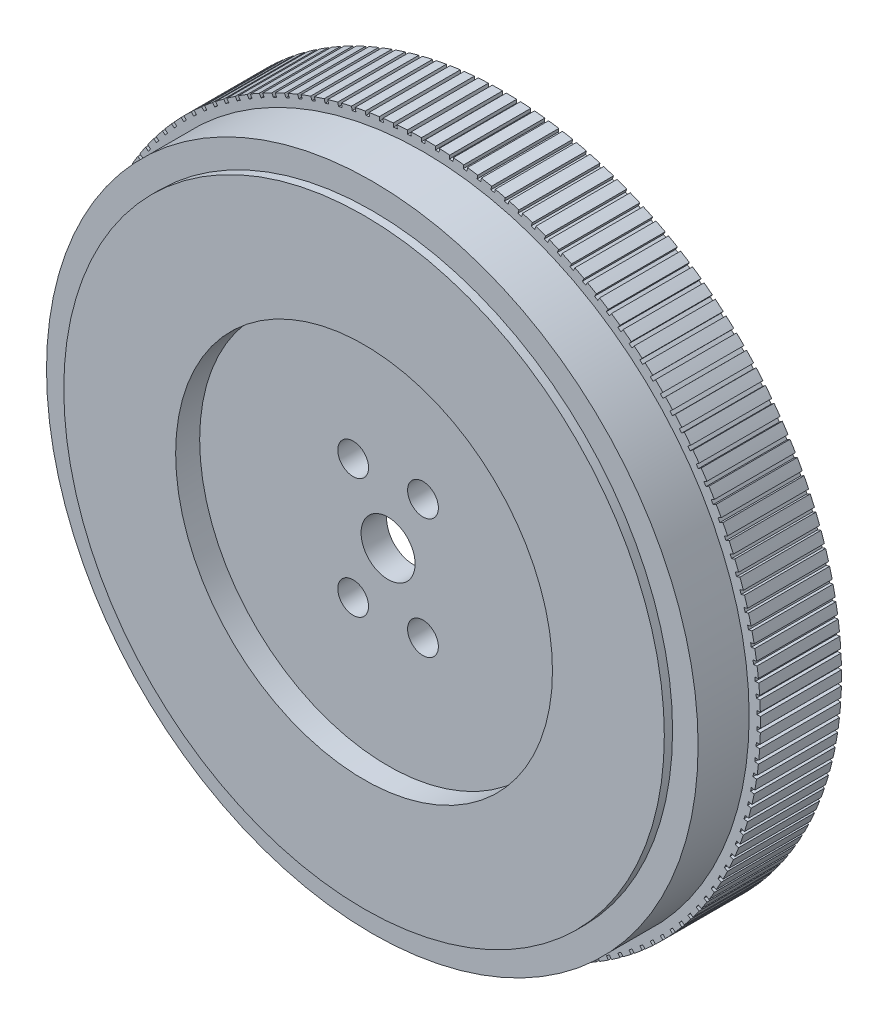
SolidWorks part; units mm, degrees
ref_plane "Front Plane" through (0, 0, 0) normal (0, 0, 1) x (1, 0, 0)
ref_plane "Top Plane" through (0, 0, 0) normal (0, 1, 0) x (1, 0, 0)
ref_plane "Right Plane" through (0, 0, 0) normal (1, 0, 0) x (0, 0, -1)
sketch "Sketch1" plane through (0, 0, 0) normal (0, 0, 1) x (1, 0, 0)
  circle A0 centre (0, 0) radius 25.1
  circle A1 centre (0, 0) radius 40
  circle A2 centre (0, 0) radius 43.4
  circle A3 centre (0, 0) radius 44.9
  dimension "D1" = 50.2
  dimension "D2" = 80
  dimension "D3" = 86.8
  dimension "D4" = 89.8
extrude "Boss-Extrude1" add sketch "Sketch1" along normal blind 10.8 contours A3
sketch "Sketch2" plane through (0, 0, 10.8) normal (0, 0, 1) x (1, 0, 0)
  circle A1 centre (0, 0) radius 44.9
  circle A3 centre (0, 0) radius 44.9
  circle A4 centre (0, 0) radius 43.4
  circle A5 centre (0, 0) radius 43.4
  dimension "D1" = 0
  dimension "D2" = 0
extrude "Boss-Extrude2" add sketch "Sketch2" along normal blind 6.8 contours A5 region at (0, 0, 10.8)
sketch "Sketch3" plane through (0, 0, 17.6) normal (0, 0, 1) x (1, 0, 0)
  circle A5 centre (0, 0) radius 40
  circle A6 centre (0, 0) radius 40
  dimension "D3" = 0
extrude "Boss-Extrude3" add sketch "Sketch3" along normal blind 1.1
sketch "Sketch4" plane through (0, 0, 18.7) normal (0, 0, 1) x (1, 0, 0)
  circle A8 centre (0, 0) radius 25.1
  circle A9 centre (0, 0) radius 25.1
  dimension "D4" = 0
extrude "Cut-Extrude1" cut sketch "Sketch4" against normal blind 3.2
sketch "Sketch5" plane through (0, 0, 0) normal (0, 0, -1) x (-1, 0, 0)
  circle A0 centre (0, 0) radius 33.85
  dimension "D1" = 67.7
extrude "Cut-Extrude2" cut sketch "Sketch5" against normal blind 12.1
sketch "Sketch6" plane through (0, 0, 15.5) normal (0, 0, 1) x (1, 0, 0)
  line L0 (0, 0) -> (0, 10.7681) construction
  line L1 (0, 0) -> (5.1297, 0) construction
  circle A0 centre (0, 0) radius 3.6
  circle A1 centre (4.65, 8) radius 2.05
  circle A2 centre (-4.65, 8) radius 2.05
  circle A3 centre (-4.65, -8) radius 2.05
  circle A4 centre (4.65, -8) radius 2.05
  dimension "D1" = 7.2
  dimension "D2" = 4.1
  dimension "D4" = 8
  dimension "D3" = 4.65
extrude "Cut-Extrude3" cut sketch "Sketch6" against normal through all
sketch "Sketch7" plane through (0, 0, 0) normal (0, 0, -1) x (-1, 0, 0)
  line L0 (0, -0.0504) -> (0, 18.0936) construction
  line L1 (1.6316, 44.8985) -> (1.6106, 44.3989)
  line L2 (-0.25, 44.9274) -> (0.25, 44.9274)
  line L3 (-0.25, 44.9274) -> (-0.25, 44.4274)
  line L4 (-0.25, 44.4274) -> (0.25, 44.4274)
  line L5 (0.25, 44.9274) -> (0.25, 44.4274)
  line L6 (-0.25, 44.9274) -> (0.25, 44.4274) construction
  line L7 (-0.25, 44.4274) -> (0.25, 44.9274) construction
  line L8 (1.6316, 44.8985) -> (2.1311, 44.8775)
  line L9 (2.1311, 44.8775) -> (2.1102, 44.378)
  line L10 (1.6106, 44.3989) -> (2.1102, 44.378)
  line L11 (3.5103, 44.7908) -> (3.4685, 44.2925)
  line L12 (3.5103, 44.7908) -> (4.0086, 44.7489)
  line L13 (4.0086, 44.7489) -> (3.9667, 44.2507)
  line L14 (3.4685, 44.2925) -> (3.9667, 44.2507)
  line L15 (5.3829, 44.6045) -> (5.3202, 44.1084)
  line L16 (5.3829, 44.6045) -> (5.8789, 44.5418)
  line L17 (5.8789, 44.5418) -> (5.8163, 44.0458)
  line L18 (5.3202, 44.1084) -> (5.8163, 44.0458)
  line L19 (7.246, 44.3399) -> (7.1626, 43.847)
  line L20 (7.246, 44.3399) -> (7.739, 44.2566)
  line L21 (7.739, 44.2566) -> (7.6556, 43.7636)
  line L22 (7.1626, 43.847) -> (7.6556, 43.7636)
  line L23 (9.0964, 43.9976) -> (8.9924, 43.5086)
  line L24 (9.0964, 43.9976) -> (9.5855, 43.8937)
  line L25 (9.5855, 43.8937) -> (9.4815, 43.4046)
  line L26 (8.9924, 43.5086) -> (9.4815, 43.4046)
  line L27 (10.9308, 43.5781) -> (10.8065, 43.0938)
  line L28 (10.9308, 43.5781) -> (11.4151, 43.4538)
  line L29 (11.4151, 43.4538) -> (11.2908, 42.9695)
  line L30 (10.8065, 43.0938) -> (11.2908, 42.9695)
  line L31 (12.7461, 43.0822) -> (12.6016, 42.6035)
  line L32 (12.7461, 43.0822) -> (13.2248, 42.9376)
  line L33 (13.2248, 42.9376) -> (13.0803, 42.459)
  line L34 (12.6016, 42.6035) -> (13.0803, 42.459)
  line L35 (14.539, 42.5106) -> (14.3746, 42.0384)
  line L36 (14.539, 42.5106) -> (15.0112, 42.3462)
  line L37 (15.0112, 42.3462) -> (14.8468, 41.874)
  line L38 (14.3746, 42.0384) -> (14.8468, 41.874)
  line L39 (16.3064, 41.8645) -> (16.1224, 41.3996)
  line L40 (16.3064, 41.8645) -> (16.7713, 41.6804)
  line L41 (16.7713, 41.6804) -> (16.5873, 41.2155)
  line L42 (16.1224, 41.3996) -> (16.5873, 41.2155)
  line L43 (18.0452, 41.1449) -> (17.8419, 40.6882)
  line L44 (18.0452, 41.1449) -> (18.502, 40.9416)
  line L45 (18.502, 40.9416) -> (18.2986, 40.4848)
  line L46 (17.8419, 40.6882) -> (18.2986, 40.4848)
  line L47 (19.7524, 40.3532) -> (19.5301, 39.9053)
  line L48 (19.7524, 40.3532) -> (20.2002, 40.1309)
  line L49 (20.2002, 40.1309) -> (19.9779, 39.683)
  line L50 (19.5301, 39.9053) -> (19.9779, 39.683)
  line L51 (21.4249, 39.4906) -> (21.184, 39.0525)
  line L52 (21.4249, 39.4906) -> (21.863, 39.2498)
  line L53 (21.863, 39.2498) -> (21.6221, 38.8116)
  line L54 (21.184, 39.0525) -> (21.6221, 38.8116)
  line L55 (23.0598, 38.5588) -> (22.8008, 38.1311)
  line L56 (23.0598, 38.5588) -> (23.4875, 38.2998)
  line L57 (23.4875, 38.2998) -> (23.2284, 37.8721)
  line L58 (22.8008, 38.1311) -> (23.2284, 37.8721)
  line L59 (24.6542, 37.5593) -> (24.3775, 37.1429)
  line L60 (24.6542, 37.5593) -> (25.0707, 37.2827)
  line L61 (25.0707, 37.2827) -> (24.794, 36.8662)
  line L62 (24.3775, 37.1429) -> (24.794, 36.8662)
  line L63 (26.2054, 36.494) -> (25.9115, 36.0895)
  line L64 (26.2054, 36.494) -> (26.6099, 36.2001)
  line L65 (26.6099, 36.2001) -> (26.316, 35.7956)
  line L66 (25.9115, 36.0895) -> (26.316, 35.7956)
  line L67 (27.7106, 35.3646) -> (27.4001, 34.9728)
  line L68 (27.7106, 35.3646) -> (28.1025, 35.054)
  line L69 (28.1025, 35.054) -> (27.7919, 34.6622)
  line L70 (27.4001, 34.9728) -> (27.7919, 34.6622)
  line L71 (29.1673, 34.1732) -> (28.8405, 33.7947)
  line L72 (29.1673, 34.1732) -> (29.5457, 33.8465)
  line L73 (29.5457, 33.8465) -> (29.219, 33.468)
  line L74 (28.8405, 33.7947) -> (29.219, 33.468)
  line L75 (30.5727, 32.9218) -> (30.2304, 32.5573)
  line L76 (30.5727, 32.9218) -> (30.9372, 32.5795)
  line L77 (30.9372, 32.5795) -> (30.5949, 32.2151)
  line L78 (30.2304, 32.5573) -> (30.5949, 32.2151)
  line L79 (31.9245, 31.6127) -> (31.5673, 31.2629)
  line L80 (31.9245, 31.6127) -> (32.2743, 31.2554)
  line L81 (32.2743, 31.2554) -> (31.9171, 30.9056)
  line L82 (31.5673, 31.2629) -> (31.9171, 30.9056)
  line L83 (33.2203, 30.2481) -> (32.8487, 29.9135)
  line L84 (33.2203, 30.2481) -> (33.5549, 29.8765)
  line L85 (33.5549, 29.8765) -> (33.1833, 29.542)
  line L86 (32.8487, 29.9135) -> (33.1833, 29.542)
  line L87 (34.4578, 28.8304) -> (34.0726, 28.5117)
  line L88 (34.4578, 28.8304) -> (34.7765, 28.4452)
  line L89 (34.7765, 28.4452) -> (34.3913, 28.1265)
  line L90 (34.0726, 28.5117) -> (34.3913, 28.1265)
  line L91 (35.6349, 27.3622) -> (35.2366, 27.0599)
  line L92 (35.6349, 27.3622) -> (35.9372, 26.9639)
  line L93 (35.9372, 26.9639) -> (35.5389, 26.6616)
  line L94 (35.2366, 27.0599) -> (35.5389, 26.6616)
  line L95 (36.7494, 25.846) -> (36.3389, 25.5606)
  line L96 (36.7494, 25.846) -> (37.0348, 25.4354)
  line L97 (37.0348, 25.4354) -> (36.6242, 25.15)
  line L98 (36.3389, 25.5606) -> (36.6242, 25.15)
  line L99 (37.7995, 24.2844) -> (37.3774, 24.0165)
  line L100 (37.7995, 24.2844) -> (38.0674, 23.8622)
  line L101 (38.0674, 23.8622) -> (37.6453, 23.5943)
  line L102 (37.3774, 24.0165) -> (37.6453, 23.5943)
  line L103 (38.7833, 22.6802) -> (38.3503, 22.4302)
  line L104 (38.7833, 22.6802) -> (39.0333, 22.2472)
  line L105 (39.0333, 22.2472) -> (38.6003, 21.9972)
  line L106 (38.3503, 22.4302) -> (38.6003, 21.9972)
  line L107 (39.699, 21.0362) -> (39.2559, 20.8046)
  line L108 (39.699, 21.0362) -> (39.9307, 20.5931)
  line L109 (39.9307, 20.5931) -> (39.4876, 20.3615)
  line L110 (39.2559, 20.8046) -> (39.4876, 20.3615)
  line L111 (40.5451, 19.3554) -> (40.0927, 19.1425)
  line L112 (40.5451, 19.3554) -> (40.758, 18.903)
  line L113 (40.758, 18.903) -> (40.3056, 18.6901)
  line L114 (40.0927, 19.1425) -> (40.3056, 18.6901)
  line L115 (41.3201, 17.6405) -> (40.8591, 17.4468)
  line L116 (41.3201, 17.6405) -> (41.5138, 17.1796)
  line L117 (41.5138, 17.1796) -> (41.0529, 16.9859)
  line L118 (40.8591, 17.4468) -> (41.0529, 16.9859)
  line L119 (42.0225, 15.8948) -> (41.5539, 15.7205)
  line L120 (42.0225, 15.8948) -> (42.1968, 15.4261)
  line L121 (42.1968, 15.4261) -> (41.7282, 15.2518)
  line L122 (41.5539, 15.7205) -> (41.7282, 15.2518)
  line L123 (42.6513, 14.1211) -> (42.1757, 13.9666)
  line L124 (42.6513, 14.1211) -> (42.8058, 13.6456)
  line L125 (42.8058, 13.6456) -> (42.3302, 13.4911)
  line L126 (42.1757, 13.9666) -> (42.3302, 13.4911)
  line L127 (43.2052, 12.3227) -> (42.7236, 12.1882)
  line L128 (43.2052, 12.3227) -> (43.3396, 11.8411)
  line L129 (43.3396, 11.8411) -> (42.8581, 11.7066)
  line L130 (42.7236, 12.1882) -> (42.8581, 11.7066)
  line L131 (43.6833, 10.5026) -> (43.1965, 10.3884)
  line L132 (43.6833, 10.5026) -> (43.7975, 10.0158)
  line L133 (43.7975, 10.0158) -> (43.3107, 9.9016)
  line L134 (43.1965, 10.3884) -> (43.3107, 9.9016)
  line L135 (44.0848, 8.6641) -> (43.5936, 8.5704)
  line L136 (44.0848, 8.6641) -> (44.1785, 8.173)
  line L137 (44.1785, 8.173) -> (43.6873, 8.0793)
  line L138 (43.5936, 8.5704) -> (43.6873, 8.0793)
  line L139 (44.4089, 6.8105) -> (43.9143, 6.7374)
  line L140 (44.4089, 6.8105) -> (44.482, 6.3158)
  line L141 (44.482, 6.3158) -> (43.9873, 6.2428)
  line L142 (43.9143, 6.7374) -> (43.9873, 6.2428)
  line L143 (44.6552, 4.9448) -> (44.1579, 4.8926)
  line L144 (44.6552, 4.9448) -> (44.7074, 4.4476)
  line L145 (44.7074, 4.4476) -> (44.2102, 4.3953)
  line L146 (44.1579, 4.8926) -> (44.2102, 4.3953)
  line L147 (44.8231, 3.0705) -> (44.3241, 3.0391)
  line L148 (44.8231, 3.0705) -> (44.8545, 2.5715)
  line L149 (44.8545, 2.5715) -> (44.3554, 2.5401)
  line L150 (44.3241, 3.0391) -> (44.3554, 2.5401)
  line L151 (44.9123, 1.1908) -> (44.4124, 1.1804)
  line L152 (44.9123, 1.1908) -> (44.9228, 0.6909)
  line L153 (44.9228, 0.6909) -> (44.4229, 0.6805)
  line L154 (44.4124, 1.1804) -> (44.4229, 0.6805)
  line L155 (44.9228, -0.6909) -> (44.4229, -0.6805)
  line L156 (44.9228, -0.6909) -> (44.9123, -1.1908)
  line L157 (44.9123, -1.1908) -> (44.4124, -1.1804)
  line L158 (44.4229, -0.6805) -> (44.4124, -1.1804)
  line L159 (44.8545, -2.5715) -> (44.3554, -2.5401)
  line L160 (44.8545, -2.5715) -> (44.8231, -3.0705)
  line L161 (44.8231, -3.0705) -> (44.3241, -3.0391)
  line L162 (44.3554, -2.5401) -> (44.3241, -3.0391)
  line L163 (44.7074, -4.4476) -> (44.2102, -4.3953)
  line L164 (44.7074, -4.4476) -> (44.6552, -4.9448)
  line L165 (44.6552, -4.9448) -> (44.1579, -4.8926)
  line L166 (44.2102, -4.3953) -> (44.1579, -4.8926)
  line L167 (44.482, -6.3158) -> (43.9873, -6.2428)
  line L168 (44.482, -6.3158) -> (44.4089, -6.8105)
  line L169 (44.4089, -6.8105) -> (43.9143, -6.7374)
  line L170 (43.9873, -6.2428) -> (43.9143, -6.7374)
  line L171 (44.1785, -8.173) -> (43.6873, -8.0793)
  line L172 (44.1785, -8.173) -> (44.0848, -8.6641)
  line L173 (44.0848, -8.6641) -> (43.5936, -8.5704)
  line L174 (43.6873, -8.0793) -> (43.5936, -8.5704)
  line L175 (43.7975, -10.0158) -> (43.3107, -9.9016)
  line L176 (43.7975, -10.0158) -> (43.6833, -10.5026)
  line L177 (43.6833, -10.5026) -> (43.1965, -10.3884)
  line L178 (43.3107, -9.9016) -> (43.1965, -10.3884)
  line L179 (43.3396, -11.8411) -> (42.8581, -11.7066)
  line L180 (43.3396, -11.8411) -> (43.2052, -12.3227)
  line L181 (43.2052, -12.3227) -> (42.7236, -12.1882)
  line L182 (42.8581, -11.7066) -> (42.7236, -12.1882)
  line L183 (42.8058, -13.6456) -> (42.3302, -13.4911)
  line L184 (42.8058, -13.6456) -> (42.6513, -14.1211)
  line L185 (42.6513, -14.1211) -> (42.1757, -13.9666)
  line L186 (42.3302, -13.4911) -> (42.1757, -13.9666)
  line L187 (42.1968, -15.4261) -> (41.7282, -15.2518)
  line L188 (42.1968, -15.4261) -> (42.0225, -15.8948)
  line L189 (42.0225, -15.8948) -> (41.5539, -15.7205)
  line L190 (41.7282, -15.2518) -> (41.5539, -15.7205)
  line L191 (41.5138, -17.1796) -> (41.0529, -16.9859)
  line L192 (41.5138, -17.1796) -> (41.3201, -17.6405)
  line L193 (41.3201, -17.6405) -> (40.8591, -17.4468)
  line L194 (41.0529, -16.9859) -> (40.8591, -17.4468)
  line L195 (40.758, -18.903) -> (40.3056, -18.6901)
  line L196 (40.758, -18.903) -> (40.5451, -19.3554)
  line L197 (40.5451, -19.3554) -> (40.0927, -19.1425)
  line L198 (40.3056, -18.6901) -> (40.0927, -19.1425)
  line L199 (39.9307, -20.5931) -> (39.4876, -20.3615)
  line L200 (39.9307, -20.5931) -> (39.699, -21.0362)
  line L201 (39.699, -21.0362) -> (39.2559, -20.8046)
  line L202 (39.4876, -20.3615) -> (39.2559, -20.8046)
  line L203 (39.0333, -22.2472) -> (38.6003, -21.9972)
  line L204 (39.0333, -22.2472) -> (38.7833, -22.6802)
  line L205 (38.7833, -22.6802) -> (38.3503, -22.4302)
  line L206 (38.6003, -21.9972) -> (38.3503, -22.4302)
  line L207 (38.0674, -23.8622) -> (37.6453, -23.5943)
  line L208 (38.0674, -23.8622) -> (37.7995, -24.2844)
  line L209 (37.7995, -24.2844) -> (37.3774, -24.0165)
  line L210 (37.6453, -23.5943) -> (37.3774, -24.0165)
  line L211 (37.0348, -25.4354) -> (36.6242, -25.15)
  line L212 (37.0348, -25.4354) -> (36.7494, -25.846)
  line L213 (36.7494, -25.846) -> (36.3389, -25.5606)
  line L214 (36.6242, -25.15) -> (36.3389, -25.5606)
  line L215 (35.9372, -26.9639) -> (35.5389, -26.6616)
  line L216 (35.9372, -26.9639) -> (35.6349, -27.3622)
  line L217 (35.6349, -27.3622) -> (35.2366, -27.0599)
  line L218 (35.5389, -26.6616) -> (35.2366, -27.0599)
  line L219 (34.7765, -28.4452) -> (34.3913, -28.1265)
  line L220 (34.7765, -28.4452) -> (34.4578, -28.8304)
  line L221 (34.4578, -28.8304) -> (34.0726, -28.5117)
  line L222 (34.3913, -28.1265) -> (34.0726, -28.5117)
  line L223 (33.5549, -29.8765) -> (33.1833, -29.542)
  line L224 (33.5549, -29.8765) -> (33.2203, -30.2481)
  line L225 (33.2203, -30.2481) -> (32.8487, -29.9135)
  line L226 (33.1833, -29.542) -> (32.8487, -29.9135)
  line L227 (32.2743, -31.2554) -> (31.9171, -30.9056)
  line L228 (32.2743, -31.2554) -> (31.9245, -31.6127)
  line L229 (31.9245, -31.6127) -> (31.5673, -31.2629)
  line L230 (31.9171, -30.9056) -> (31.5673, -31.2629)
  line L231 (30.9372, -32.5795) -> (30.5949, -32.2151)
  line L232 (30.9372, -32.5795) -> (30.5727, -32.9218)
  line L233 (30.5727, -32.9218) -> (30.2304, -32.5573)
  line L234 (30.5949, -32.2151) -> (30.2304, -32.5573)
  line L235 (29.5457, -33.8465) -> (29.219, -33.468)
  line L236 (29.5457, -33.8465) -> (29.1673, -34.1732)
  line L237 (29.1673, -34.1732) -> (28.8405, -33.7947)
  line L238 (29.219, -33.468) -> (28.8405, -33.7947)
  line L239 (28.1025, -35.054) -> (27.7919, -34.6622)
  line L240 (28.1025, -35.054) -> (27.7106, -35.3646)
  line L241 (27.7106, -35.3646) -> (27.4001, -34.9728)
  line L242 (27.7919, -34.6622) -> (27.4001, -34.9728)
  line L243 (26.6099, -36.2001) -> (26.316, -35.7956)
  line L244 (26.6099, -36.2001) -> (26.2054, -36.494)
  line L245 (26.2054, -36.494) -> (25.9115, -36.0895)
  line L246 (26.316, -35.7956) -> (25.9115, -36.0895)
  line L247 (25.0707, -37.2827) -> (24.794, -36.8662)
  line L248 (25.0707, -37.2827) -> (24.6542, -37.5593)
  line L249 (24.6542, -37.5593) -> (24.3775, -37.1429)
  line L250 (24.794, -36.8662) -> (24.3775, -37.1429)
  line L251 (23.4875, -38.2998) -> (23.2284, -37.8721)
  line L252 (23.4875, -38.2998) -> (23.0598, -38.5588)
  line L253 (23.0598, -38.5588) -> (22.8008, -38.1311)
  line L254 (23.2284, -37.8721) -> (22.8008, -38.1311)
  line L255 (21.863, -39.2498) -> (21.6221, -38.8116)
  line L256 (21.863, -39.2498) -> (21.4249, -39.4906)
  line L257 (21.4249, -39.4906) -> (21.184, -39.0525)
  line L258 (21.6221, -38.8116) -> (21.184, -39.0525)
  line L259 (20.2002, -40.1309) -> (19.9779, -39.683)
  line L260 (20.2002, -40.1309) -> (19.7524, -40.3532)
  line L261 (19.7524, -40.3532) -> (19.5301, -39.9053)
  line L262 (19.9779, -39.683) -> (19.5301, -39.9053)
  line L263 (18.502, -40.9416) -> (18.2986, -40.4848)
  line L264 (18.502, -40.9416) -> (18.0452, -41.1449)
  line L265 (18.0452, -41.1449) -> (17.8419, -40.6882)
  line L266 (18.2986, -40.4848) -> (17.8419, -40.6882)
  line L267 (16.7713, -41.6804) -> (16.5873, -41.2155)
  line L268 (16.7713, -41.6804) -> (16.3064, -41.8645)
  line L269 (16.3064, -41.8645) -> (16.1224, -41.3996)
  line L270 (16.5873, -41.2155) -> (16.1224, -41.3996)
  line L271 (15.0112, -42.3462) -> (14.8468, -41.874)
  line L272 (15.0112, -42.3462) -> (14.539, -42.5106)
  line L273 (14.539, -42.5106) -> (14.3746, -42.0384)
  line L274 (14.8468, -41.874) -> (14.3746, -42.0384)
  line L275 (13.2248, -42.9376) -> (13.0803, -42.459)
  line L276 (13.2248, -42.9376) -> (12.7461, -43.0822)
  line L277 (12.7461, -43.0822) -> (12.6016, -42.6035)
  line L278 (13.0803, -42.459) -> (12.6016, -42.6035)
  line L279 (11.4151, -43.4538) -> (11.2908, -42.9695)
  line L280 (11.4151, -43.4538) -> (10.9308, -43.5781)
  line L281 (10.9308, -43.5781) -> (10.8065, -43.0938)
  line L282 (11.2908, -42.9695) -> (10.8065, -43.0938)
  line L283 (9.5855, -43.8937) -> (9.4815, -43.4046)
  line L284 (9.5855, -43.8937) -> (9.0964, -43.9976)
  line L285 (9.0964, -43.9976) -> (8.9924, -43.5086)
  line L286 (9.4815, -43.4046) -> (8.9924, -43.5086)
  line L287 (7.739, -44.2566) -> (7.6556, -43.7636)
  line L288 (7.739, -44.2566) -> (7.246, -44.3399)
  line L289 (7.246, -44.3399) -> (7.1626, -43.847)
  line L290 (7.6556, -43.7636) -> (7.1626, -43.847)
  line L291 (5.8789, -44.5418) -> (5.8163, -44.0458)
  line L292 (5.8789, -44.5418) -> (5.3829, -44.6045)
  line L293 (5.3829, -44.6045) -> (5.3202, -44.1084)
  line L294 (5.8163, -44.0458) -> (5.3202, -44.1084)
  line L295 (4.0086, -44.7489) -> (3.9667, -44.2507)
  line L296 (4.0086, -44.7489) -> (3.5103, -44.7908)
  line L297 (3.5103, -44.7908) -> (3.4685, -44.2925)
  line L298 (3.9667, -44.2507) -> (3.4685, -44.2925)
  line L299 (2.1311, -44.8775) -> (2.1102, -44.378)
  line L300 (2.1311, -44.8775) -> (1.6316, -44.8985)
  line L301 (1.6316, -44.8985) -> (1.6106, -44.3989)
  line L302 (2.1102, -44.378) -> (1.6106, -44.3989)
  line L303 (0.25, -44.9274) -> (0.25, -44.4274)
  line L304 (0.25, -44.9274) -> (-0.25, -44.9274)
  line L305 (-0.25, -44.9274) -> (-0.25, -44.4274)
  line L306 (0.25, -44.4274) -> (-0.25, -44.4274)
  line L307 (-1.6316, -44.8985) -> (-1.6106, -44.3989)
  line L308 (-1.6316, -44.8985) -> (-2.1311, -44.8775)
  line L309 (-2.1311, -44.8775) -> (-2.1102, -44.378)
  line L310 (-1.6106, -44.3989) -> (-2.1102, -44.378)
  line L311 (-3.5103, -44.7908) -> (-3.4685, -44.2925)
  line L312 (-3.5103, -44.7908) -> (-4.0086, -44.7489)
  line L313 (-4.0086, -44.7489) -> (-3.9667, -44.2507)
  line L314 (-3.4685, -44.2925) -> (-3.9667, -44.2507)
  line L315 (-5.3829, -44.6045) -> (-5.3202, -44.1084)
  line L316 (-5.3829, -44.6045) -> (-5.8789, -44.5418)
  line L317 (-5.8789, -44.5418) -> (-5.8163, -44.0458)
  line L318 (-5.3202, -44.1084) -> (-5.8163, -44.0458)
  line L319 (-7.246, -44.3399) -> (-7.1626, -43.847)
  line L320 (-7.246, -44.3399) -> (-7.739, -44.2566)
  line L321 (-7.739, -44.2566) -> (-7.6556, -43.7636)
  line L322 (-7.1626, -43.847) -> (-7.6556, -43.7636)
  line L323 (-9.0964, -43.9976) -> (-8.9924, -43.5086)
  line L324 (-9.0964, -43.9976) -> (-9.5855, -43.8937)
  line L325 (-9.5855, -43.8937) -> (-9.4815, -43.4046)
  line L326 (-8.9924, -43.5086) -> (-9.4815, -43.4046)
  line L327 (-10.9308, -43.5781) -> (-10.8065, -43.0938)
  line L328 (-10.9308, -43.5781) -> (-11.4151, -43.4538)
  line L329 (-11.4151, -43.4538) -> (-11.2908, -42.9695)
  line L330 (-10.8065, -43.0938) -> (-11.2908, -42.9695)
  line L331 (-12.7461, -43.0822) -> (-12.6016, -42.6035)
  line L332 (-12.7461, -43.0822) -> (-13.2248, -42.9376)
  line L333 (-13.2248, -42.9376) -> (-13.0803, -42.459)
  line L334 (-12.6016, -42.6035) -> (-13.0803, -42.459)
  line L335 (-14.539, -42.5106) -> (-14.3746, -42.0384)
  line L336 (-14.539, -42.5106) -> (-15.0112, -42.3462)
  line L337 (-15.0112, -42.3462) -> (-14.8468, -41.874)
  line L338 (-14.3746, -42.0384) -> (-14.8468, -41.874)
  line L339 (-16.3064, -41.8645) -> (-16.1224, -41.3996)
  line L340 (-16.3064, -41.8645) -> (-16.7713, -41.6804)
  line L341 (-16.7713, -41.6804) -> (-16.5873, -41.2155)
  line L342 (-16.1224, -41.3996) -> (-16.5873, -41.2155)
  line L343 (-18.0452, -41.1449) -> (-17.8419, -40.6882)
  line L344 (-18.0452, -41.1449) -> (-18.502, -40.9416)
  line L345 (-18.502, -40.9416) -> (-18.2986, -40.4848)
  line L346 (-17.8419, -40.6882) -> (-18.2986, -40.4848)
  line L347 (-19.7524, -40.3532) -> (-19.5301, -39.9053)
  line L348 (-19.7524, -40.3532) -> (-20.2002, -40.1309)
  line L349 (-20.2002, -40.1309) -> (-19.9779, -39.683)
  line L350 (-19.5301, -39.9053) -> (-19.9779, -39.683)
  line L351 (-21.4249, -39.4906) -> (-21.184, -39.0525)
  line L352 (-21.4249, -39.4906) -> (-21.863, -39.2498)
  line L353 (-21.863, -39.2498) -> (-21.6221, -38.8116)
  line L354 (-21.184, -39.0525) -> (-21.6221, -38.8116)
  line L355 (-23.0598, -38.5588) -> (-22.8008, -38.1311)
  line L356 (-23.0598, -38.5588) -> (-23.4875, -38.2998)
  line L357 (-23.4875, -38.2998) -> (-23.2284, -37.8721)
  line L358 (-22.8008, -38.1311) -> (-23.2284, -37.8721)
  line L359 (-24.6542, -37.5593) -> (-24.3775, -37.1429)
  line L360 (-24.6542, -37.5593) -> (-25.0707, -37.2827)
  line L361 (-25.0707, -37.2827) -> (-24.794, -36.8662)
  line L362 (-24.3775, -37.1429) -> (-24.794, -36.8662)
  line L363 (-26.2054, -36.494) -> (-25.9115, -36.0895)
  line L364 (-26.2054, -36.494) -> (-26.6099, -36.2001)
  line L365 (-26.6099, -36.2001) -> (-26.316, -35.7956)
  line L366 (-25.9115, -36.0895) -> (-26.316, -35.7956)
  line L367 (-27.7106, -35.3646) -> (-27.4001, -34.9728)
  line L368 (-27.7106, -35.3646) -> (-28.1025, -35.054)
  line L369 (-28.1025, -35.054) -> (-27.7919, -34.6622)
  line L370 (-27.4001, -34.9728) -> (-27.7919, -34.6622)
  line L371 (-29.1673, -34.1732) -> (-28.8405, -33.7947)
  line L372 (-29.1673, -34.1732) -> (-29.5457, -33.8465)
  line L373 (-29.5457, -33.8465) -> (-29.219, -33.468)
  line L374 (-28.8405, -33.7947) -> (-29.219, -33.468)
  line L375 (-30.5727, -32.9218) -> (-30.2304, -32.5573)
  line L376 (-30.5727, -32.9218) -> (-30.9372, -32.5795)
  line L377 (-30.9372, -32.5795) -> (-30.5949, -32.2151)
  line L378 (-30.2304, -32.5573) -> (-30.5949, -32.2151)
  line L379 (-31.9245, -31.6127) -> (-31.5673, -31.2629)
  line L380 (-31.9245, -31.6127) -> (-32.2743, -31.2554)
  line L381 (-32.2743, -31.2554) -> (-31.9171, -30.9056)
  line L382 (-31.5673, -31.2629) -> (-31.9171, -30.9056)
  line L383 (-33.2203, -30.2481) -> (-32.8487, -29.9135)
  line L384 (-33.2203, -30.2481) -> (-33.5549, -29.8765)
  line L385 (-33.5549, -29.8765) -> (-33.1833, -29.542)
  line L386 (-32.8487, -29.9135) -> (-33.1833, -29.542)
  line L387 (-34.4578, -28.8304) -> (-34.0726, -28.5117)
  line L388 (-34.4578, -28.8304) -> (-34.7765, -28.4452)
  line L389 (-34.7765, -28.4452) -> (-34.3913, -28.1265)
  line L390 (-34.0726, -28.5117) -> (-34.3913, -28.1265)
  line L391 (-35.6349, -27.3622) -> (-35.2366, -27.0599)
  line L392 (-35.6349, -27.3622) -> (-35.9372, -26.9639)
  line L393 (-35.9372, -26.9639) -> (-35.5389, -26.6616)
  line L394 (-35.2366, -27.0599) -> (-35.5389, -26.6616)
  line L395 (-36.7494, -25.846) -> (-36.3389, -25.5606)
  line L396 (-36.7494, -25.846) -> (-37.0348, -25.4354)
  line L397 (-37.0348, -25.4354) -> (-36.6242, -25.15)
  line L398 (-36.3389, -25.5606) -> (-36.6242, -25.15)
  line L399 (-37.7995, -24.2844) -> (-37.3774, -24.0165)
  line L400 (-37.7995, -24.2844) -> (-38.0674, -23.8622)
  line L401 (-38.0674, -23.8622) -> (-37.6453, -23.5943)
  line L402 (-37.3774, -24.0165) -> (-37.6453, -23.5943)
  line L403 (-38.7833, -22.6802) -> (-38.3503, -22.4302)
  line L404 (-38.7833, -22.6802) -> (-39.0333, -22.2472)
  line L405 (-39.0333, -22.2472) -> (-38.6003, -21.9972)
  line L406 (-38.3503, -22.4302) -> (-38.6003, -21.9972)
  line L407 (-39.699, -21.0362) -> (-39.2559, -20.8046)
  line L408 (-39.699, -21.0362) -> (-39.9307, -20.5931)
  line L409 (-39.9307, -20.5931) -> (-39.4876, -20.3615)
  line L410 (-39.2559, -20.8046) -> (-39.4876, -20.3615)
  line L411 (-40.5451, -19.3554) -> (-40.0927, -19.1425)
  line L412 (-40.5451, -19.3554) -> (-40.758, -18.903)
  line L413 (-40.758, -18.903) -> (-40.3056, -18.6901)
  line L414 (-40.0927, -19.1425) -> (-40.3056, -18.6901)
  line L415 (-41.3201, -17.6405) -> (-40.8591, -17.4468)
  line L416 (-41.3201, -17.6405) -> (-41.5138, -17.1796)
  line L417 (-41.5138, -17.1796) -> (-41.0529, -16.9859)
  line L418 (-40.8591, -17.4468) -> (-41.0529, -16.9859)
  line L419 (-42.0225, -15.8948) -> (-41.5539, -15.7205)
  line L420 (-42.0225, -15.8948) -> (-42.1968, -15.4261)
  line L421 (-42.1968, -15.4261) -> (-41.7282, -15.2518)
  line L422 (-41.5539, -15.7205) -> (-41.7282, -15.2518)
  line L423 (-42.6513, -14.1211) -> (-42.1757, -13.9666)
  line L424 (-42.6513, -14.1211) -> (-42.8058, -13.6456)
  line L425 (-42.8058, -13.6456) -> (-42.3302, -13.4911)
  line L426 (-42.1757, -13.9666) -> (-42.3302, -13.4911)
  line L427 (-43.2052, -12.3227) -> (-42.7236, -12.1882)
  line L428 (-43.2052, -12.3227) -> (-43.3396, -11.8411)
  line L429 (-43.3396, -11.8411) -> (-42.8581, -11.7066)
  line L430 (-42.7236, -12.1882) -> (-42.8581, -11.7066)
  line L431 (-43.6833, -10.5026) -> (-43.1965, -10.3884)
  line L432 (-43.6833, -10.5026) -> (-43.7975, -10.0158)
  line L433 (-43.7975, -10.0158) -> (-43.3107, -9.9016)
  line L434 (-43.1965, -10.3884) -> (-43.3107, -9.9016)
  line L435 (-44.0848, -8.6641) -> (-43.5936, -8.5704)
  line L436 (-44.0848, -8.6641) -> (-44.1785, -8.173)
  line L437 (-44.1785, -8.173) -> (-43.6873, -8.0793)
  line L438 (-43.5936, -8.5704) -> (-43.6873, -8.0793)
  line L439 (-44.4089, -6.8105) -> (-43.9143, -6.7374)
  line L440 (-44.4089, -6.8105) -> (-44.482, -6.3158)
  line L441 (-44.482, -6.3158) -> (-43.9873, -6.2428)
  line L442 (-43.9143, -6.7374) -> (-43.9873, -6.2428)
  line L443 (-44.6552, -4.9448) -> (-44.1579, -4.8926)
  line L444 (-44.6552, -4.9448) -> (-44.7074, -4.4476)
  line L445 (-44.7074, -4.4476) -> (-44.2102, -4.3953)
  line L446 (-44.1579, -4.8926) -> (-44.2102, -4.3953)
  line L447 (-44.8231, -3.0705) -> (-44.3241, -3.0391)
  line L448 (-44.8231, -3.0705) -> (-44.8545, -2.5715)
  line L449 (-44.8545, -2.5715) -> (-44.3554, -2.5401)
  line L450 (-44.3241, -3.0391) -> (-44.3554, -2.5401)
  line L451 (-44.9123, -1.1908) -> (-44.4124, -1.1804)
  line L452 (-44.9123, -1.1908) -> (-44.9228, -0.6909)
  line L453 (-44.9228, -0.6909) -> (-44.4229, -0.6805)
  line L454 (-44.4124, -1.1804) -> (-44.4229, -0.6805)
  line L455 (-44.9228, 0.6909) -> (-44.4229, 0.6805)
  line L456 (-44.9228, 0.6909) -> (-44.9123, 1.1908)
  line L457 (-44.9123, 1.1908) -> (-44.4124, 1.1804)
  line L458 (-44.4229, 0.6805) -> (-44.4124, 1.1804)
  line L459 (-44.8545, 2.5715) -> (-44.3554, 2.5401)
  line L460 (-44.8545, 2.5715) -> (-44.8231, 3.0705)
  line L461 (-44.8231, 3.0705) -> (-44.3241, 3.0391)
  line L462 (-44.3554, 2.5401) -> (-44.3241, 3.0391)
  line L463 (-44.7074, 4.4476) -> (-44.2102, 4.3953)
  line L464 (-44.7074, 4.4476) -> (-44.6552, 4.9448)
  line L465 (-44.6552, 4.9448) -> (-44.1579, 4.8926)
  line L466 (-44.2102, 4.3953) -> (-44.1579, 4.8926)
  line L467 (-44.482, 6.3158) -> (-43.9873, 6.2428)
  line L468 (-44.482, 6.3158) -> (-44.4089, 6.8105)
  line L469 (-44.4089, 6.8105) -> (-43.9143, 6.7374)
  line L470 (-43.9873, 6.2428) -> (-43.9143, 6.7374)
  line L471 (-44.1785, 8.173) -> (-43.6873, 8.0793)
  line L472 (-44.1785, 8.173) -> (-44.0848, 8.6641)
  line L473 (-44.0848, 8.6641) -> (-43.5936, 8.5704)
  line L474 (-43.6873, 8.0793) -> (-43.5936, 8.5704)
  line L475 (-43.7975, 10.0158) -> (-43.3107, 9.9016)
  line L476 (-43.7975, 10.0158) -> (-43.6833, 10.5026)
  line L477 (-43.6833, 10.5026) -> (-43.1965, 10.3884)
  line L478 (-43.3107, 9.9016) -> (-43.1965, 10.3884)
  line L479 (-43.3396, 11.8411) -> (-42.8581, 11.7066)
  line L480 (-43.3396, 11.8411) -> (-43.2052, 12.3227)
  line L481 (-43.2052, 12.3227) -> (-42.7236, 12.1882)
  line L482 (-42.8581, 11.7066) -> (-42.7236, 12.1882)
  line L483 (-42.8058, 13.6456) -> (-42.3302, 13.4911)
  line L484 (-42.8058, 13.6456) -> (-42.6513, 14.1211)
  line L485 (-42.6513, 14.1211) -> (-42.1757, 13.9666)
  line L486 (-42.3302, 13.4911) -> (-42.1757, 13.9666)
  line L487 (-42.1968, 15.4261) -> (-41.7282, 15.2518)
  line L488 (-42.1968, 15.4261) -> (-42.0225, 15.8948)
  line L489 (-42.0225, 15.8948) -> (-41.5539, 15.7205)
  line L490 (-41.7282, 15.2518) -> (-41.5539, 15.7205)
  line L491 (-41.5138, 17.1796) -> (-41.0529, 16.9859)
  line L492 (-41.5138, 17.1796) -> (-41.3201, 17.6405)
  line L493 (-41.3201, 17.6405) -> (-40.8591, 17.4468)
  line L494 (-41.0529, 16.9859) -> (-40.8591, 17.4468)
  line L495 (-40.758, 18.903) -> (-40.3056, 18.6901)
  line L496 (-40.758, 18.903) -> (-40.5451, 19.3554)
  line L497 (-40.5451, 19.3554) -> (-40.0927, 19.1425)
  line L498 (-40.3056, 18.6901) -> (-40.0927, 19.1425)
  line L499 (-39.9307, 20.5931) -> (-39.4876, 20.3615)
  line L500 (-39.9307, 20.5931) -> (-39.699, 21.0362)
  line L501 (-39.699, 21.0362) -> (-39.2559, 20.8046)
  line L502 (-39.4876, 20.3615) -> (-39.2559, 20.8046)
  line L503 (-39.0333, 22.2472) -> (-38.6003, 21.9972)
  line L504 (-39.0333, 22.2472) -> (-38.7833, 22.6802)
  line L505 (-38.7833, 22.6802) -> (-38.3503, 22.4302)
  line L506 (-38.6003, 21.9972) -> (-38.3503, 22.4302)
  line L507 (-38.0674, 23.8622) -> (-37.6453, 23.5943)
  line L508 (-38.0674, 23.8622) -> (-37.7995, 24.2844)
  line L509 (-37.7995, 24.2844) -> (-37.3774, 24.0165)
  line L510 (-37.6453, 23.5943) -> (-37.3774, 24.0165)
  line L511 (-37.0348, 25.4354) -> (-36.6242, 25.15)
  line L512 (-37.0348, 25.4354) -> (-36.7494, 25.846)
  line L513 (-36.7494, 25.846) -> (-36.3389, 25.5606)
  line L514 (-36.6242, 25.15) -> (-36.3389, 25.5606)
  line L515 (-35.9372, 26.9639) -> (-35.5389, 26.6616)
  line L516 (-35.9372, 26.9639) -> (-35.6349, 27.3622)
  line L517 (-35.6349, 27.3622) -> (-35.2366, 27.0599)
  line L518 (-35.5389, 26.6616) -> (-35.2366, 27.0599)
  line L519 (-34.7765, 28.4452) -> (-34.3913, 28.1265)
  line L520 (-34.7765, 28.4452) -> (-34.4578, 28.8304)
  line L521 (-34.4578, 28.8304) -> (-34.0726, 28.5117)
  line L522 (-34.3913, 28.1265) -> (-34.0726, 28.5117)
  line L523 (-33.5549, 29.8765) -> (-33.1833, 29.542)
  line L524 (-33.5549, 29.8765) -> (-33.2203, 30.2481)
  line L525 (-33.2203, 30.2481) -> (-32.8487, 29.9135)
  line L526 (-33.1833, 29.542) -> (-32.8487, 29.9135)
  line L527 (-32.2743, 31.2554) -> (-31.9171, 30.9056)
  line L528 (-32.2743, 31.2554) -> (-31.9245, 31.6127)
  line L529 (-31.9245, 31.6127) -> (-31.5673, 31.2629)
  line L530 (-31.9171, 30.9056) -> (-31.5673, 31.2629)
  line L531 (-30.9372, 32.5795) -> (-30.5949, 32.2151)
  line L532 (-30.9372, 32.5795) -> (-30.5727, 32.9218)
  line L533 (-30.5727, 32.9218) -> (-30.2304, 32.5573)
  line L534 (-30.5949, 32.2151) -> (-30.2304, 32.5573)
  line L535 (-29.5457, 33.8465) -> (-29.219, 33.468)
  line L536 (-29.5457, 33.8465) -> (-29.1673, 34.1732)
  line L537 (-29.1673, 34.1732) -> (-28.8405, 33.7947)
  line L538 (-29.219, 33.468) -> (-28.8405, 33.7947)
  line L539 (-28.1025, 35.054) -> (-27.7919, 34.6622)
  line L540 (-28.1025, 35.054) -> (-27.7106, 35.3646)
  line L541 (-27.7106, 35.3646) -> (-27.4001, 34.9728)
  line L542 (-27.7919, 34.6622) -> (-27.4001, 34.9728)
  line L543 (-26.6099, 36.2001) -> (-26.316, 35.7956)
  line L544 (-26.6099, 36.2001) -> (-26.2054, 36.494)
  line L545 (-26.2054, 36.494) -> (-25.9115, 36.0895)
  line L546 (-26.316, 35.7956) -> (-25.9115, 36.0895)
  line L547 (-25.0707, 37.2827) -> (-24.794, 36.8662)
  line L548 (-25.0707, 37.2827) -> (-24.6542, 37.5593)
  line L549 (-24.6542, 37.5593) -> (-24.3775, 37.1429)
  line L550 (-24.794, 36.8662) -> (-24.3775, 37.1429)
  line L551 (-23.4875, 38.2998) -> (-23.2284, 37.8721)
  line L552 (-23.4875, 38.2998) -> (-23.0598, 38.5588)
  line L553 (-23.0598, 38.5588) -> (-22.8008, 38.1311)
  line L554 (-23.2284, 37.8721) -> (-22.8008, 38.1311)
  line L555 (-21.863, 39.2498) -> (-21.6221, 38.8116)
  line L556 (-21.863, 39.2498) -> (-21.4249, 39.4906)
  line L557 (-21.4249, 39.4906) -> (-21.184, 39.0525)
  line L558 (-21.6221, 38.8116) -> (-21.184, 39.0525)
  line L559 (-20.2002, 40.1309) -> (-19.9779, 39.683)
  line L560 (-20.2002, 40.1309) -> (-19.7524, 40.3532)
  line L561 (-19.7524, 40.3532) -> (-19.5301, 39.9053)
  line L562 (-19.9779, 39.683) -> (-19.5301, 39.9053)
  line L563 (-18.502, 40.9416) -> (-18.2986, 40.4848)
  line L564 (-18.502, 40.9416) -> (-18.0452, 41.1449)
  line L565 (-18.0452, 41.1449) -> (-17.8419, 40.6882)
  line L566 (-18.2986, 40.4848) -> (-17.8419, 40.6882)
  line L567 (-16.7713, 41.6804) -> (-16.5873, 41.2155)
  line L568 (-16.7713, 41.6804) -> (-16.3064, 41.8645)
  line L569 (-16.3064, 41.8645) -> (-16.1224, 41.3996)
  line L570 (-16.5873, 41.2155) -> (-16.1224, 41.3996)
  line L571 (-15.0112, 42.3462) -> (-14.8468, 41.874)
  line L572 (-15.0112, 42.3462) -> (-14.539, 42.5106)
  line L573 (-14.539, 42.5106) -> (-14.3746, 42.0384)
  line L574 (-14.8468, 41.874) -> (-14.3746, 42.0384)
  line L575 (-13.2248, 42.9376) -> (-13.0803, 42.459)
  line L576 (-13.2248, 42.9376) -> (-12.7461, 43.0822)
  line L577 (-12.7461, 43.0822) -> (-12.6016, 42.6035)
  line L578 (-13.0803, 42.459) -> (-12.6016, 42.6035)
  line L579 (-11.4151, 43.4538) -> (-11.2908, 42.9695)
  line L580 (-11.4151, 43.4538) -> (-10.9308, 43.5781)
  line L581 (-10.9308, 43.5781) -> (-10.8065, 43.0938)
  line L582 (-11.2908, 42.9695) -> (-10.8065, 43.0938)
  line L583 (-9.5855, 43.8937) -> (-9.4815, 43.4046)
  line L584 (-9.5855, 43.8937) -> (-9.0964, 43.9976)
  line L585 (-9.0964, 43.9976) -> (-8.9924, 43.5086)
  line L586 (-9.4815, 43.4046) -> (-8.9924, 43.5086)
  line L587 (-7.739, 44.2566) -> (-7.6556, 43.7636)
  line L588 (-7.739, 44.2566) -> (-7.246, 44.3399)
  line L589 (-7.246, 44.3399) -> (-7.1626, 43.847)
  line L590 (-7.6556, 43.7636) -> (-7.1626, 43.847)
  line L591 (-5.8789, 44.5418) -> (-5.8163, 44.0458)
  line L592 (-5.8789, 44.5418) -> (-5.3829, 44.6045)
  line L593 (-5.3829, 44.6045) -> (-5.3202, 44.1084)
  line L594 (-5.8163, 44.0458) -> (-5.3202, 44.1084)
  line L595 (-4.0086, 44.7489) -> (-3.9667, 44.2507)
  line L596 (-4.0086, 44.7489) -> (-3.5103, 44.7908)
  line L597 (-3.5103, 44.7908) -> (-3.4685, 44.2925)
  line L598 (-3.9667, 44.2507) -> (-3.4685, 44.2925)
  line L599 (-2.1311, 44.8775) -> (-2.1102, 44.378)
  line L600 (-2.1311, 44.8775) -> (-1.6316, 44.8985)
  line L601 (-1.6316, 44.8985) -> (-1.6106, 44.3989)
  line L602 (-2.1102, 44.378) -> (-1.6106, 44.3989)
  point P1 (0, 44.6774)
  point P607 (0, 0)
  dimension "D1" = 0.5
  dimension "D2" = 0.5
  dimension "D3" = 150
extrude "Cut-Extrude4" cut sketch "Sketch7" against normal through all
